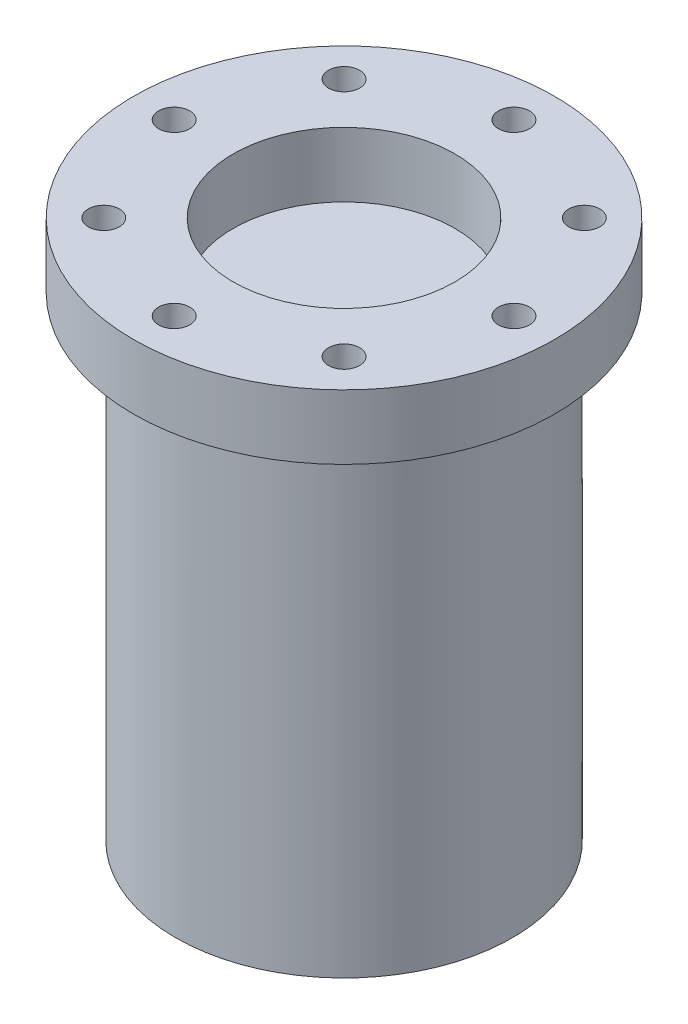
SolidWorks part; units mm, degrees
ref_plane "Front Plane" through (0, 0, 0) normal (0, 0, 1) x (1, 0, 0)
ref_plane "Top Plane" through (0, 0, 0) normal (0, 1, 0) x (1, 0, 0)
ref_plane "Right Plane" through (0, 0, 0) normal (1, 0, 0) x (0, 0, -1)
sketch "Sketch1" plane through (0, 0, 0) normal (0, 1, 0) x (1, 0, 0)
  circle A0 centre (0, 0) radius 57.15
  dimension "D1" = 114.3
extrude "Extrude-Thin1" add sketch "Sketch1" along normal blind 17.526 thin thin type one direction reverse wall 27.051
sketch "Sketch2" plane through (0, 0, 0) normal (0, 1, 0) x (1, 0, 0)
  circle A0 centre (0, 46.101) radius 4.2164
extrude "Cut-Extrude2" cut sketch "Sketch2" along normal blind 17.526
ref_axis "Axis1" through (0, 58.677, 0) along (0, -1, 0)
pattern_circular "CirPattern1" count 8 over 360 about axis through (0, 58.677, 0) along (0, -1, 0) of "Cut-Extrude2"
sketch "Sketch4" plane through (0, 0, 0) normal (0, 1, 0) x (1, 0, 0)
  line L0 (0, 0) -> (0, 46.8507)
ref_plane "Plane1" through (0, 0, 0) normal (0, -1, 0) x (1, 0, 0)
sketch "Sketch5" plane through (0, 0, 0) normal (0, -1, 0) x (1, 0, 0)
  circle A0 centre (0, 0) radius 45.72
  dimension "D1" = 91.44
extrude "Extrude1" add sketch "Sketch5" along normal blind 128.778
